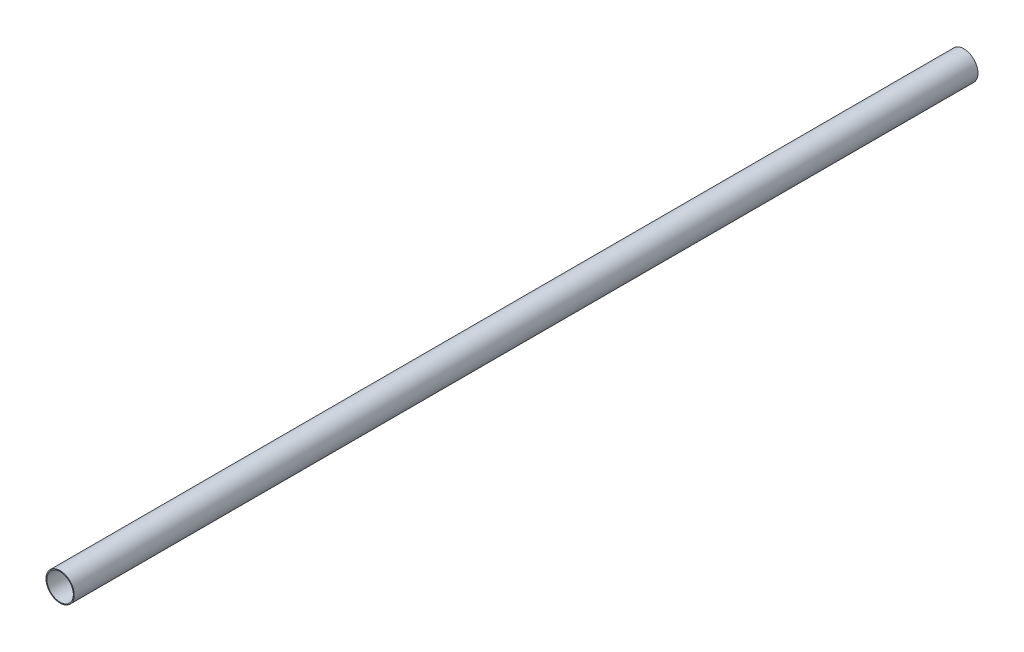
SolidWorks part; units mm, degrees
ref_plane "Front Plane" through (0, 0, 0) normal (0, 0, 1) x (1, 0, 0)
ref_plane "Top Plane" through (0, 0, 0) normal (0, 1, 0) x (1, 0, 0)
ref_plane "Right Plane" through (0, 0, 0) normal (1, 0, 0) x (0, 0, -1)
sketch "Sketch1" plane through (0, 0, 0) normal (0, 0, 1) x (1, 0, 0)
  line L0 (-14.2875, 0) -> (14.2875, 0) construction
  line L1 (0, 0) -> (0, 1.0456) construction
  point P0 (-13.3985, 0)
  point P4 (0, 0)
  point P6 (13.3985, 0)
  dimension "OD" = 28.575
  dimension "ID" = 26.797
sketch "Sketch2" plane through (0, 0, 0) normal (0, 0, 1) x (1, 0, 0)
  line L0 (-14.2875, 0) -> (14.2875, 0) construction
  circle A0 centre (0, 0) radius 13.3985
  circle A1 centre (0, 0) radius 14.2875
  dimension "D1" = 26.797
  dimension "D2" = 28.575
extrude "Boss-Extrude1" add sketch "Sketch2" along normal mid plane 914.4
sketch "Sketch3" plane through (0, 0, 0) normal (1, 0, 0) x (0, 0, -1)
  line L0 (457.2, 0) -> (-457.2, 0) construction
  line L1 (-457.2, 14.2875) -> (-457.2, -14.2875) construction
  line L2 (0, 0) -> (0, 21.8825) construction
  point P0 (-452.628, 0)
  point P6 (0, 0)
  point P8 (452.628, 0)
  dimension "D1" = 905.256
ref_axis "Center Axis 1" through (0, 0, 457.2) along (0, 0, -1)
ref_plane "Contact Plane 1" through (0, 0, 457.2) normal (0, 0, 1) x (1, 0, 0)
ref_plane "Contact Plane 2" through (0, 0, -457.2) normal (0, 0, -1) x (-1, 0, 0)
equation "\"D1@Sketch2\"=\"ID@Sketch1\""
equation "\"D2@Sketch2\"=\"OD@Sketch1\""
equation "\"D1@Sketch3\"=\"Length@Boss-Extrude1\"*0.99"
